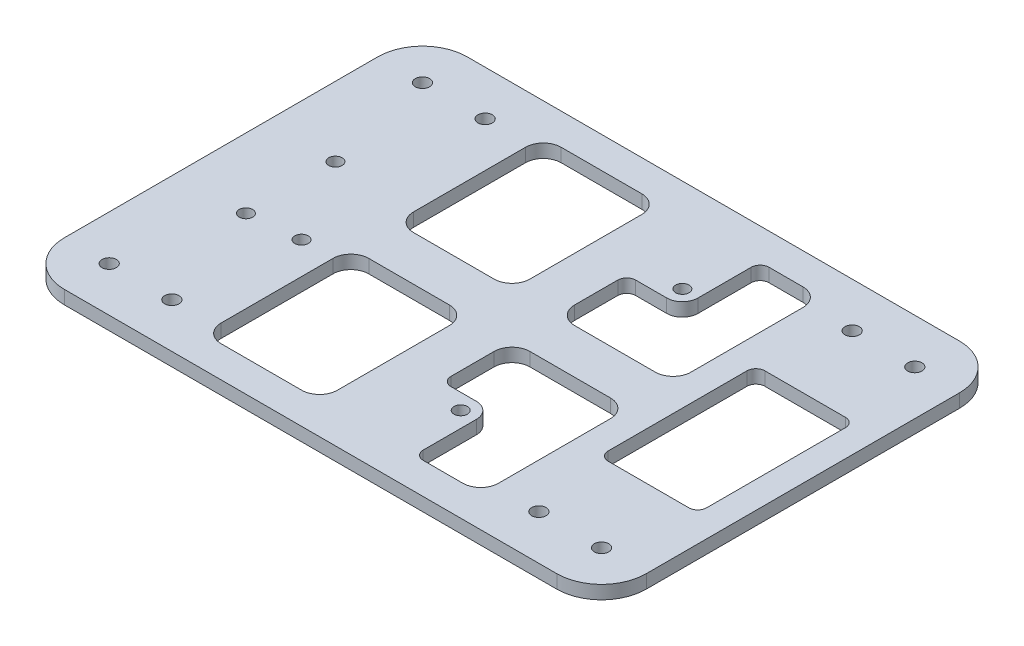
SolidWorks part; units mm, degrees
ref_plane "Front Plane" through (0, 0, 0) normal (0, 0, 1) x (1, 0, 0)
ref_plane "Top Plane" through (0, 0, 0) normal (0, 1, 0) x (1, 0, 0)
ref_plane "Right Plane" through (0, 0, 0) normal (1, 0, 0) x (0, 0, -1)
sketch "Sketch2" plane through (0, 0, 0) normal (0, 1, 0) x (1, 0, 0)
  line L1 (6.2712, 10.565) -> (136.2712, 10.565)
  line L2 (6.2712, 10.565) -> (6.2712, 100.565)
  line L3 (6.2712, 100.565) -> (136.2712, 100.565)
  line L4 (136.2712, 10.565) -> (136.2712, 100.565)
  dimension "D1" = 130
  dimension "D2" = 90
extrude "Boss-Extrude1" add sketch "Sketch2" against normal blind 3
sketch "Sketch3" plane through (0, 0, 0) normal (0, 1, 0) x (1, 0, 0)
  line L0 (71.2712, 100.565) -> (71.2712, 10.565) construction
  line L1 (136.2712, 100.565) -> (6.2712, 100.565) construction
  line L2 (6.2712, 10.565) -> (136.2712, 10.565) construction
  line L3 (6.2712, 55.565) -> (136.2712, 55.565) construction
  line L4 (6.2712, 100.565) -> (6.2712, 10.565) construction
  line L5 (136.2712, 10.565) -> (136.2712, 100.565) construction
  line L7 (112.2712, 63.565) -> (126.2712, 63.565) construction
  line L8 (112.2712, 63.565) -> (112.2712, 47.565) construction
  line L9 (112.2712, 47.565) -> (126.2712, 47.565) construction
  line L10 (126.2712, 63.565) -> (126.2712, 47.565) construction
  circle A0 centre (126.2712, 63.565) radius 1.5
  circle A1 centre (126.2712, 47.565) radius 1.5
  circle A2 centre (112.2712, 47.565) radius 1.5
  circle A3 centre (112.2712, 63.565) radius 1.5
  circle A4 centre (16.2712, 47.565) radius 1.5
  circle A5 centre (30.2712, 47.565) radius 1.5
  circle A6 centre (16.2712, 63.565) radius 1.5
  circle A7 centre (30.2712, 63.565) radius 1.5
  point P16 (112.2712, 55.565)
  dimension "D4" = 3
  dimension "D1" = 14
  dimension "D2" = 16
  dimension "D3" = 10
extrude "Cut-Extrude1" cut sketch "Sketch3" against normal blind 10 contours A6 | A7 | A4 | A5 | A0 | A3 | A2 | A1
sketch "Sketch4" plane through (0, 0, 0) normal (0, 1, 0) x (1, 0, 0)
  line L0 (16.2712, 47.565) -> (16.2712, 10.565) construction
  line L1 (6.2712, 10.565) -> (136.2712, 10.565) construction
  line L2 (30.2712, 47.565) -> (30.2712, 10.565) construction
  line L3 (6.2712, 55.565) -> (136.2712, 55.565) construction
  line L4 (136.2712, 100.565) -> (6.2712, 100.565) construction
  line L5 (6.2712, 100.565) -> (6.2712, 10.565) construction
  line L6 (71.2712, 100.565) -> (71.2712, 10.565) construction
  line L7 (16.2712, 20.565) -> (71.2712, 20.565) construction
  line L8 (136.2712, 10.565) -> (136.2712, 100.565) construction
  circle A0 centre (16.2712, 20.565) radius 1.6
  circle A1 centre (30.2712, 20.565) radius 1.6
  circle A2 centre (30.2712, 90.565) radius 1.6
  circle A3 centre (16.2712, 90.565) radius 1.6
  circle A4 centre (112.2712, 20.565) radius 1.6
  circle A5 centre (126.2712, 20.565) radius 1.6
  circle A6 centre (126.2712, 90.565) radius 1.6
  circle A7 centre (112.2712, 90.565) radius 1.6
  point P23 (30.2712, 20.565)
  dimension "D2" = 3.2
  dimension "D1" = 10
extrude "Cut-Extrude2" cut sketch "Sketch4" against normal blind 10
fillet "Fillet1" radius 10 4 edges at (136.2712, -1.5, -100.565) (6.2712, -1.5, -100.565) (6.2712, -1.5, -10.565) (136.2712, -1.5, -10.565)
sketch "Sketch5" plane through (0, 0, 0) normal (0, 1, 0) x (1, 0, 0)
  line L0 (71.2712, 100.565) -> (71.2712, 10.565) construction
  line L1 (126.2712, 100.565) -> (16.2712, 100.565) construction
  line L2 (16.2712, 10.565) -> (126.2712, 10.565) construction
  line L3 (6.2712, 55.565) -> (136.2712, 55.565) construction
  line L4 (6.2712, 90.565) -> (6.2712, 20.565) construction
  line L5 (136.2712, 20.565) -> (136.2712, 90.565) construction
  line L6 (76.2712, 89.565) -> (76.2712, 64.565)
  line L7 (80.2712, 60.565) -> (98.2712, 60.565)
  line L9 (80.2712, 93.565) -> (98.2712, 93.565)
  line L10 (102.2712, 89.565) -> (102.2712, 64.565)
  line L11 (40.2712, 89.565) -> (40.2712, 64.565)
  line L12 (62.2712, 93.565) -> (44.2712, 93.565)
  line L13 (62.2712, 60.565) -> (44.2712, 60.565)
  line L14 (66.2712, 89.565) -> (66.2712, 64.565)
  line L15 (66.2712, 21.565) -> (66.2712, 46.565)
  line L16 (62.2712, 50.565) -> (44.2712, 50.565)
  line L17 (62.2712, 17.565) -> (44.2712, 17.565)
  line L18 (40.2712, 21.565) -> (40.2712, 46.565)
  line L19 (102.2712, 21.565) -> (102.2712, 46.565)
  line L20 (80.2712, 17.565) -> (98.2712, 17.565)
  line L21 (80.2712, 50.565) -> (98.2712, 50.565)
  line L22 (76.2712, 21.565) -> (76.2712, 46.565)
  circle A0 centre (112.2712, 90.565) radius 1.6 construction
  arc A1 (102.2712, 89.565) -> (98.2712, 93.565) centre (98.2712, 89.565) ccw
  arc A2 (102.2712, 64.565) -> (98.2712, 60.565) centre (98.2712, 64.565) cw
  arc A3 (80.2712, 60.565) -> (76.2712, 64.565) centre (80.2712, 64.565) cw
  arc A4 (76.2712, 89.565) -> (80.2712, 93.565) centre (80.2712, 89.565) cw
  arc A5 (66.2712, 89.565) -> (62.2712, 93.565) centre (62.2712, 89.565) ccw
  arc A6 (62.2712, 60.565) -> (66.2712, 64.565) centre (62.2712, 64.565) ccw
  arc A7 (40.2712, 64.565) -> (44.2712, 60.565) centre (44.2712, 64.565) ccw
  arc A8 (40.2712, 89.565) -> (44.2712, 93.565) centre (44.2712, 89.565) cw
  arc A9 (40.2712, 21.565) -> (44.2712, 17.565) centre (44.2712, 21.565) ccw
  arc A10 (40.2712, 46.565) -> (44.2712, 50.565) centre (44.2712, 46.565) cw
  arc A11 (62.2712, 50.565) -> (66.2712, 46.565) centre (62.2712, 46.565) cw
  arc A12 (66.2712, 21.565) -> (62.2712, 17.565) centre (62.2712, 21.565) cw
  arc A13 (76.2712, 21.565) -> (80.2712, 17.565) centre (80.2712, 21.565) ccw
  arc A14 (80.2712, 50.565) -> (76.2712, 46.565) centre (80.2712, 46.565) ccw
  arc A15 (102.2712, 46.565) -> (98.2712, 50.565) centre (98.2712, 46.565) ccw
  arc A16 (102.2712, 21.565) -> (98.2712, 17.565) centre (98.2712, 21.565) cw
  dimension "D5" = 4
  dimension "D1" = 5
  dimension "D2" = 5
  dimension "D3" = 10
  dimension "D4" = 7
extrude "Cut-Extrude3" cut sketch "Sketch5" against normal blind 10
sketch "Sketch6" plane through (0, 0, 0) normal (0, 1, 0) x (1, 0, 0)
  line L0 (136.2712, 55.565) -> (6.2712, 55.565) construction
  line L1 (33.1361, 46.675) -> (83.9361, 46.675) construction
  line L2 (33.1361, 46.675) -> (33.1361, 31.435) construction
  line L3 (33.1361, 31.435) -> (83.9361, 31.435) construction
  line L4 (83.9361, 46.675) -> (83.9361, 31.435) construction
  line L5 (33.1361, 46.675) -> (85.2061, 46.675) construction
  line L6 (33.1361, 46.675) -> (33.1361, 79.695) construction
  line L7 (33.1361, 79.695) -> (85.2061, 79.695) construction
  line L8 (85.2061, 46.675) -> (85.2061, 79.695) construction
  line L9 (86.7061, 81.195) -> (31.6361, 81.195) construction
  line L10 (86.7061, 81.195) -> (86.7061, 29.935) construction
  line L11 (86.7061, 29.935) -> (31.6361, 29.935) construction
  line L12 (31.6361, 81.195) -> (31.6361, 29.935) construction
  line L13 (136.2712, 20.565) -> (136.2712, 90.565) construction
  line L14 (6.2712, 90.565) -> (6.2712, 20.565) construction
  line L15 (71.2712, 10.565) -> (71.2712, 100.565) construction
  line L16 (16.2712, 10.565) -> (126.2712, 10.565) construction
  line L17 (126.2712, 100.565) -> (16.2712, 100.565) construction
  line L18 (76.2712, 46.565) -> (76.2712, 21.565) construction
  line L20 (87.4361, 34.935) -> (76.2712, 34.935)
  line L22 (87.4361, 34.935) -> (87.4361, 17.565)
  line L23 (76.2712, 89.565) -> (76.2712, 64.565) construction
  line L24 (88.7061, 93.565) -> (76.2712, 93.565)
  line L31 (87.4361, 17.565) -> (76.2712, 17.565)
  line L32 (76.2712, 34.935) -> (76.2712, 17.565)
  line L37 (80.2712, 17.565) -> (98.2712, 17.565) construction
  line L38 (88.7061, 93.565) -> (88.7061, 76.195)
  line L39 (88.7061, 76.195) -> (76.2712, 76.195)
  line L40 (76.2712, 93.565) -> (76.2712, 76.195)
  line L41 (98.2712, 93.565) -> (80.2712, 93.565) construction
  circle A0 centre (33.1361, 46.675) radius 1.5
  circle A1 centre (83.9361, 31.435) radius 1.5
  circle A2 centre (85.2061, 79.695) radius 1.5
  circle A3 centre (85.2061, 79.695) radius 3.5
  circle A4 centre (83.9361, 31.435) radius 3.5
  circle A5 centre (33.1361, 46.675) radius 3.5
  circle A6 centre (30.2712, 47.565) radius 1.5
  circle A7 centre (30.2712, 47.565) radius 1.5 construction
  circle A8 centre (16.2712, 47.565) radius 1.5
  circle A9 centre (16.2712, 63.565) radius 1.5
  circle A10 centre (30.2712, 63.565) radius 1.5
  circle A11 centre (112.2712, 47.565) radius 1.5
  circle A12 centre (112.2712, 63.565) radius 1.5
  circle A13 centre (126.2712, 63.565) radius 1.5
  circle A14 centre (126.2712, 47.565) radius 1.5
  point P26 (86.7061, 55.565)
  dimension "D1" = 3
  dimension "D2" = 15.24
  dimension "D3" = 50.8
  dimension "D4" = 33.02
  dimension "D5" = 52.07
  dimension "D6" = 2
extrude "Boss-Extrude4" add sketch "Sketch6" against normal up to surface (3 mm away) contours A3 L38 L24 L40 L39 | A3 A2 | A4 L20 L32 L31 L22 | A4 A1 | A6 A5 | A5 A6 | A10 | A9 | A8 | A14 | A13 | A12 | A11 region at (81.2467, 0, -24.8083) region at (86.341, 0, -33.8398) region at (81.8089, 0, -86.1398) region at (87.611, 0, -77.2901) region at (30.6788, 0, -47.4383) region at (29.461, 0, -47.8166) region at (16.2712, 0, -47.565) region at (16.2712, 0, -63.565) region at (30.2712, 0, -63.565) region at (112.2712, 0, -63.565) region at (126.2712, 0, -63.565) region at (126.2712, 0, -47.565) up to face at (89.2712, -3, -34.065)
extrude "Cut-Extrude4" cut sketch "Sketch6<6>" against normal up to surface (3 mm away) contours A0 region at (33.1361, 0, -46.675) up to face at (89.426, -3, -35.3813)
sketch "Sketch6<6>" plane through (0, 0, 0) normal (0, 1, 0) x (1, 0, 0) same geometry as "Sketch6"
sketch "Sketch8" plane through (0, 0, 0) normal (0, 1, 0) x (1, 0, 0)
  line L0 (6.2712, 55.565) -> (136.2712, 55.565) construction
  line L1 (6.2712, 90.565) -> (6.2712, 20.565) construction
  line L2 (136.2712, 20.565) -> (136.2712, 90.565) construction
  line L3 (21.8212, 67.065) -> (21.8212, 44.065) construction
  line L4 (23.8212, 67.065) -> (8.2712, 67.065)
  line L5 (23.8212, 67.065) -> (23.8212, 44.065)
  line L6 (23.8212, 44.065) -> (8.2712, 44.065)
  line L7 (8.2712, 67.065) -> (8.2712, 44.065)
  circle A0 centre (21.8212, 65.565) radius 1.5
  circle A1 centre (21.8212, 45.565) radius 1.5
  point P18 (23.8212, 55.565)
  dimension "D1" = 3
  dimension "D2" = 3
  dimension "D3" = 15.55
  dimension "D4" = 20
  dimension "D5" = 2
  dimension "D6" = 2
extrude "Cut-Extrude5" cut sketch "Sketch8" against normal blind 10 contours A0 | A1 region at (21.8212, 0, -65.565) region at (21.8212, 0, -45.565)
sketch "Sketch9" plane through (0, 0, 0) normal (0, 1, 0) x (1, 0, 0)
  line L0 (6.2712, 55.565) -> (136.2712, 55.565) construction
  line L1 (6.2712, 90.565) -> (6.2712, 20.565) construction
  line L2 (136.2712, 20.565) -> (136.2712, 90.565) construction
  line L3 (112.2712, 90.565) -> (126.2712, 90.565) construction
  line L4 (119.2712, 90.565) -> (119.2712, 55.565) construction
  line L6 (108.2712, 73.065) -> (130.2712, 73.065)
  line L7 (108.2712, 73.065) -> (108.2712, 38.065)
  line L8 (108.2712, 38.065) -> (130.2712, 38.065)
  line L9 (130.2712, 73.065) -> (130.2712, 38.065)
  point P16 (119.2712, 73.065)
  point P17 (130.2712, 55.565)
  dimension "D1" = 6
extrude "Cut-Extrude6" cut sketch "Sketch9" against normal blind 10
fillet "Fillet2" radius 2 8 edges at (76.2712, -1.5, -34.935) (87.4361, -1.5, -17.565) (88.7061, -1.5, -93.565) (76.2712, -1.5, -76.195) (130.2712, -1.5, -38.065) (108.2712, -1.5, -38.065) (130.2712, -1.5, -73.065) (108.2712, -1.5, -73.065)
